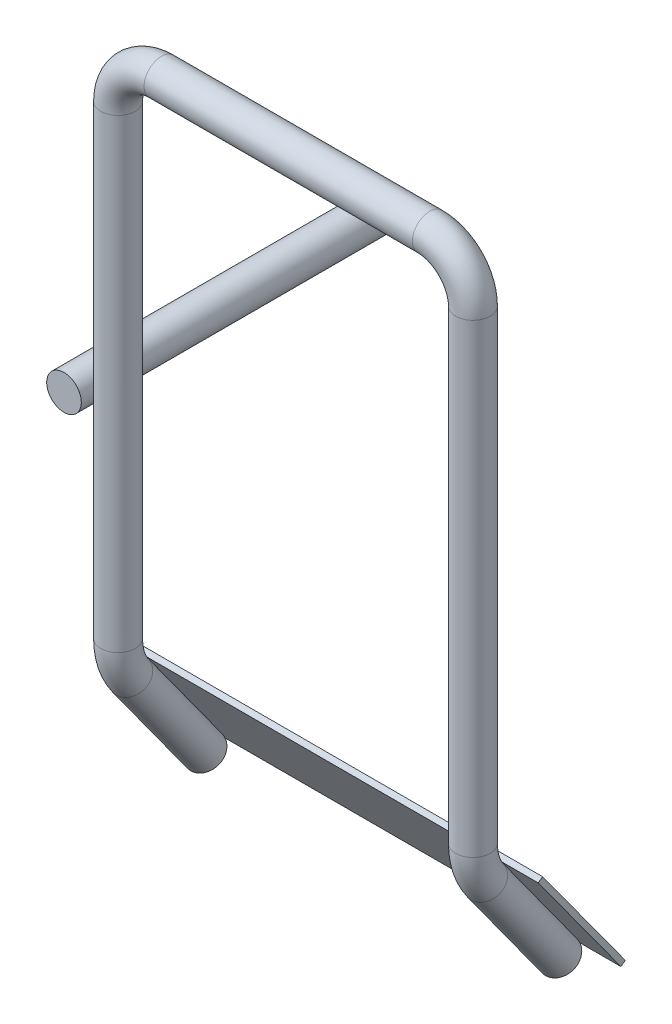
SolidWorks part; units mm, degrees
material "Chrome Stainless Steel"
ref_plane "Front Plane" through (0, 0, 0) normal (0, 0, 1) x (1, 0, 0)
ref_plane "Top Plane" through (0, 0, 0) normal (0, 1, 0) x (1, 0, 0)
ref_plane "Right Plane" through (0, 0, 0) normal (1, 0, 0) x (0, 0, -1)
ref_plane "Plane1" through (0, 0, 17) normal (0, 0, 1) x (1, 0, 0)
ref_axis "Axis1" through (-89.24, 0, 17) along (1, 0, 0)
sketch3d "3DSketch3"
  line L0 (8.2, 0, 17) -> (8.2, 4.7415, 20.4305)
  line L1 (8.2, 6.5, 21) -> (8.2, 28, 21)
  line L2 (6.2, 30, 21) -> (-6.2, 30, 21)
  line L3 (-8.2, 28, 21) -> (-8.2, 6.5, 21)
  line L4 (-8.2, 4.7415, 20.4305) -> (-8.2, 0, 17)
  line L5 (-89.24, 0, 17) -> (88.74, 0, 17) construction
  arc A0 (8.2, 4.7415, 20.4305) -> (8.2, 6.5, 21) centre (8.2, 6.5, 18) ccw
  arc A1 (-8.2, 6.5, 21) -> (-8.2, 4.7415, 20.4305) centre (-8.2, 6.5, 18) ccw
  arc A2 (-8.2, 28, 21) -> (-6.2, 30, 21) centre (-6.2, 28, 21) ccw
  arc A3 (8.2, 28, 21) -> (6.2, 30, 21) centre (6.2, 28, 21) ccw
  point P10 (8.2, 5.5285, 21)
  point P11 (5.2, 6.5, 18)
  point P14 (-8.2, 5.5285, 21)
  point P15 (-5.2, 6.5, 18)
  point P18 (-8.2, 30, 21)
  point P19 (-6.2, 28, 19)
  point P22 (8.2, 30, 21)
  point P23 (6.2, 28, 23)
  dimension "D4" = 3
  dimension "D8" = 2
  dimension "D1" = 8.2
  dimension "D2" = 8.2
  dimension "D3" = 4
  dimension "D5" = 6.5
  dimension "D6" = 6.5
  dimension "D7" = 30
ref_plane "Plane2" through (8.2, 0, 17) normal (0, 0.8102, 0.5862) x (-1, 0, 0)
sketch "Sketch2" plane through (8.2, 0, 17) normal (0, 0.8102, 0.5862) x (-1, 0, 0)
  circle A0 centre (0, 0) radius 0.8
  dimension "D1" = 1.6
sweep "Sweep1" add profiles "Sketch2" path "3DSketch3"
sketch "Sketch3" plane through (0, 0, 17) normal (0, 0, 1) x (1, 0, 0)
  line L0 (0, -55) -> (0, 55) construction
  circle A0 centre (-9.7, 16.1004) radius 0.8
  dimension "D2" = 1.6
  dimension "D1" = 9.7
extrude "Extrude1" add sketch "Sketch3" along normal blind 5 and the other way blind 10
sketch "Sketch4" plane through (0, 0, 0) normal (1, 0, 0) x (0, 0, -1)
  line L0 (-19.7824, 5.2104) -> (-15.9618, -0.0482)
  line L1 (8.25, 0) -> (-8.25, 0) construction
  dimension "D1" = 6.5
  dimension "D2" = 54
extrude "Extrude-Thin1" add sketch "Sketch4" along normal blind 10 and the other way blind 10 separate body thin thin type one direction reverse wall 0.25
